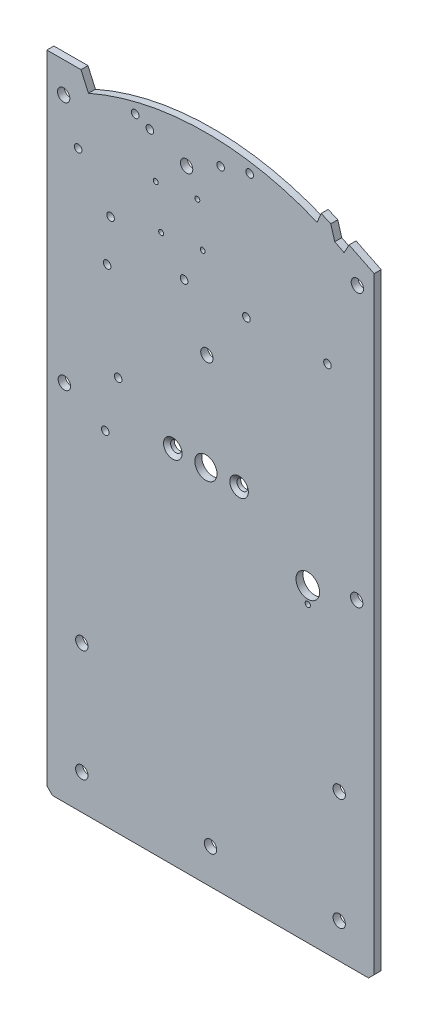
SolidWorks part; units mm, degrees
material "6061-T6 (SS)"
ref_plane "Front Plane" through (0, 0, 0) normal (0, 0, 1) x (1, 0, 0)
ref_plane "Top Plane" through (0, 0, 0) normal (0, 1, 0) x (1, 0, 0)
ref_plane "Right Plane" through (0, 0, 0) normal (1, 0, 0) x (0, 0, -1)
sketch "Sketch1" plane through (0, 0, 0) normal (0, 0, 1) x (1, 0, 0)
  line L0 (-37.0142, -65.193) -> (-37.0142, -242.993)
  line L1 (111.7057, -78.8372) -> (111.7057, -242.993)
  line L2 (111.7057, -242.993) -> (-37.0142, -242.993)
  line L3 (-28.4308, -65.1684) -> (-21.4969, -65.1485)
  line L4 (-21.4969, -65.1485) -> (-20.0556, -68.4088)
  line L41 (111.7057, -78.8372) -> (100.3159, -73.2191)
  line L42 (100.3159, -73.2191) -> (98.0489, -77.4075)
  line L43 (93.8204, -75.2164) -> (91.992, -69.0732)
  line L44 (91.992, -69.0732) -> (87.6255, -67.1718)
  line L45 (87.6255, -67.1718) -> (85.8005, -71.5708)
  line L46 (-18.13, -72.7646) -> (-20.0556, -68.4088)
  line L47 (-25.8634, -70.9762) -> (-28.4308, -65.1684) construction
  line L48 (-28.4308, -65.1684) -> (-37.0142, -65.193)
  line L75 (-20.0556, -68.4088) -> (-25.8634, -70.9762) construction
  arc A5 (98.0489, -77.4075) -> (93.8204, -75.2164) centre (35.2286, -193.468) ccw
  arc A9 (85.8005, -71.5708) -> (-18.13, -72.7646) centre (35.2286, -193.468) ccw
  dimension "D2" = 177.8
  dimension "D1" = 148.72
extrude "Boss-Extrude1" add sketch "Sketch1" against normal blind 3.175
sketch "Sketch2" plane through (0, 0, 0) normal (0, 0, 1) x (1, 0, 0)
  line L0 (111.7057, -231.472) -> (111.7057, -78.8372) construction
  line L1 (-21.4969, -65.1485) -> (-37.0142, -65.193) construction
  circle A0 centre (35.2684, -193.372) radius 5.0419
  dimension "D1" = 10.0838
  dimension "D2" = 76.4373
  dimension "D3" = 128.3861
extrude "Cut-Extrude1" cut sketch "Sketch2" against normal through all
hole_wizard "#4 Clearance Hole1" positions "Sketch4" profile "Sketch3" hole size "#4" standard "ANSI Inch" end condition through all
sketch "Sketch4" plane through (0, 0, 0) normal (0, 0, 1) x (1, 0, 0)
  point P0 (41.9398, -71.4888)
  point P3 (9.7895, -73.0113)
  point P6 (90.4886, -124.9671)
  point P9 (53.6587, -125.0729)
  point P12 (25.3388, -124.3417)
  point P15 (-9.6344, -135.8882)
  point P19 (55.1452, -67.7003)
  point P23 (3.102, -70.2707)
sketch "Sketch3" plane through (41.9398, -71.4888, 0) normal (1, 0, 0) x (0, -1, 0)
  line L0 (0, 0) -> (0, 3.175)
  line L1 (0, 3.175) -> (1.7272, 3.175)
  line L2 (1.7272, 3.175) -> (1.7272, 0)
  line L5 (1.7272, 0) -> (0, 0)
  line L11 (0, -6.35) -> (0, 107.95) construction
  dimension "Thru Hole Dia." = 3.4544
  dimension "Thru Hole Depth" = 3.175
hole_wizard "#10 Clearance Hole1" positions "Sketch6" profile "Sketch5" hole size "#10" standard "ANSI Inch" end condition through all
sketch "Sketch6" plane through (0, 0, 0) normal (0, 0, 1) x (1, 0, 0)
  point P0 (-29.3942, -79.072)
  point P3 (104.0857, -87.327)
  point P9 (35.696, -148.922)
  point P12 (26.4858, -79.072)
sketch "Sketch5" plane through (-29.3942, -79.072, 0) normal (1, 0, 0) x (0, -1, 0)
  line L0 (0, 0) -> (0, 3.175)
  line L1 (0, 3.175) -> (2.8067, 3.175)
  line L2 (2.8067, 3.175) -> (2.8067, 0)
  line L5 (2.8067, 0) -> (0, 0)
  line L11 (0, -6.35) -> (0, 107.95) construction
  dimension "Thru Hole Dia." = 5.6134
  dimension "Thru Hole Depth" = 3.175
hole_wizard "#4 Clearance Hole2" positions "Sketch8" profile "Sketch7" hole size "#4" standard "ANSI Inch" end condition through all
sketch "Sketch8" plane through (0, 0, 0) normal (0, 0, 1) x (1, 0, 0)
  point P0 (-8.0737, -116.3194)
  point P3 (-22.8122, -96.7821)
  point P12 (-10.4786, -201.738)
  point P15 (-4.604, -177.9805)
sketch "Sketch7" plane through (-8.0737, -116.3194, 0) normal (1, 0, 0) x (0, -1, 0)
  line L0 (0, 0) -> (0, 3.175)
  line L1 (0, 3.175) -> (1.7272, 3.175)
  line L2 (1.7272, 3.175) -> (1.7272, 0)
  line L5 (1.7272, 0) -> (0, 0)
  line L11 (0, -6.35) -> (0, 107.95) construction
  dimension "Thru Hole Dia." = 3.4544
  dimension "Thru Hole Depth" = 3.175
hole_wizard "27/64 (0.42188) Diameter Hole1" positions "Sketch10" profile "Sketch9" hole size "27/64" standard "ANSI Inch" end condition through all
sketch "Sketch10" plane through (0, 0, 0) normal (0, 0, 1) x (1, 0, 0)
  point P0 (81.5512, -216.6701)
sketch "Sketch9" plane through (81.5512, -216.6701, 0) normal (1, 0, 0) x (0, -1, 0)
  line L0 (0, 0) -> (0, 3.175)
  line L1 (0, 3.175) -> (5.3579, 3.175)
  line L2 (5.3579, 3.175) -> (5.3579, 0)
  line L5 (5.3579, 0) -> (0, 0)
  line L11 (0, -6.35) -> (0, 107.95) construction
  dimension "Thru Hole Dia." = 10.7158
  dimension "Thru Hole Depth" = 3.175
hole_wizard "3/32 (0.09375) Diameter Hole1" positions "Sketch12" profile "Sketch11" hole size "3/32" standard "ANSI Inch" end condition through all
sketch "Sketch12" plane through (0, 0, 0) normal (0, 0, 1) x (1, 0, 0)
  circle A0 centre (81.5512, -216.6701) radius 5.3579 construction
  point P0 (81.5512, -224.0361)
  dimension "D1" = 7.366
sketch "Sketch11" plane through (81.5512, -224.0361, 0) normal (1, 0, 0) x (0, -1, 0)
  line L0 (0, 0) -> (0, 3.175)
  line L1 (0, 3.175) -> (1.1906, 3.175)
  line L2 (1.1906, 3.175) -> (1.1906, 0)
  line L5 (1.1906, 0) -> (0, 0)
  line L11 (0, -6.35) -> (0, 107.95) construction
  dimension "Thru Hole Dia." = 2.3812
  dimension "Thru Hole Depth" = 3.175
hole_wizard "#10 Clearance Hole2" positions "Sketch14" profile "Sketch13" hole size "#10" standard "ANSI Inch" end condition through all
sketch "Sketch14" plane through (0, 0, 0) normal (0, 0, 1) x (1, 0, 0)
  circle A0 centre (-29.0767, -192.193) radius 2.8067 construction
  circle A1 centre (103.7682, -211.243) radius 2.8067 construction
  point P0 (-29.0767, -192.193)
  point P6 (103.7682, -211.243)
sketch "Sketch13" plane through (-29.0767, -192.193, 0) normal (1, 0, 0) x (0, -1, 0)
  line L0 (0, 0) -> (0, 3.175)
  line L1 (0, 3.175) -> (2.8067, 3.175)
  line L2 (2.8067, 3.175) -> (2.8067, 0)
  line L5 (2.8067, 0) -> (0, 0)
  line L11 (0, -6.35) -> (0, 107.95) construction
  dimension "Thru Hole Dia." = 5.6134
  dimension "Thru Hole Depth" = 3.175
sketch "Sketch15" plane through (0, 0, 0) normal (0, 0, 1) x (1, 0, 0)
  line L0 (109.1657, -357.293) -> (-34.4742, -357.293) construction
  line L1 (-37.0142, -242.993) -> (111.7057, -242.993)
  line L2 (-37.0142, -242.993) -> (-37.0142, -357.293)
  line L3 (-37.0142, -357.293) -> (111.7057, -357.293)
  line L4 (111.7057, -242.993) -> (111.7057, -357.293)
extrude "Boss-Extrude2" add sketch "Sketch15" against normal through all
chamfer "Chamfer1" distance 2.54 angle 45 2 edges at (-37.0142, -357.293, -1.5875) (111.7057, -357.293, -1.5875)
hole_wizard "#10 Clearance Hole3" positions "Sketch16" profile "Sketch17" hole size "#10" standard "ANSI Inch" end condition through all
sketch "Sketch16" plane through (0, 0, 0) normal (0, 0, 1) x (1, 0, 0)
  point P0 (95.8307, -341.418)
  point P3 (37.3457, -341.418)
  point P6 (-21.1392, -341.418)
  point P9 (95.8307, -290.618)
  point P12 (-21.1392, -290.618)
sketch "Sketch17" plane through (95.8307, -341.418, 0) normal (1, 0, 0) x (0, -1, 0)
  line L0 (0, 0) -> (0, 3.175)
  line L1 (0, 3.175) -> (2.8067, 3.175)
  line L2 (2.8067, 3.175) -> (2.8067, 0)
  line L5 (2.8067, 0) -> (0, 0)
  line L11 (0, -6.35) -> (0, 107.95) construction
  dimension "Thru Hole Dia." = 5.6134
  dimension "Thru Hole Depth" = 3.175
hole_wizard "CSK for #8 Flat Head Machine Screw (100)2" positions "Sketch18" profile "Sketch19" countersink size "#8" standard "ANSI Inch" end condition through all
sketch "Sketch18" plane through (0, 0, 0) normal (0, 0, 1) x (1, 0, 0)
  circle A0 centre (20.203, -193.372) radius 4.2164 construction
  circle A1 centre (50.3338, -193.372) radius 4.2164 construction
  point P0 (20.203, -193.372)
  point P2 (50.3338, -193.372)
sketch "Sketch19" plane through (20.203, -193.372, 0) normal (1, 0, 0) x (0, -1, 0)
  line L0 (0, 0) -> (0, 3.175)
  line L1 (0, 3.175) -> (2.4574, 3.175)
  line L2 (2.4574, 3.175) -> (2.4574, 1.4759)
  line L3 (2.4574, 1.4759) -> (4.2164, 0)
  line L5 (4.2164, 0) -> (0, 0)
  line L6 (-2.4574, 1.4759) -> (-4.2164, 0) construction
  line L11 (0, -6.35) -> (0, 107.95) construction
  dimension "Thru Hole Dia." = 4.9149
  dimension "Thru Hole Depth" = 3.175
  dimension "Near C'Sink Dia." = 8.4328
  dimension "Near C'Sink Angle" = 100
hole_wizard "#4-40 Tapped Hole1" positions "Sketch20" profile "Sketch21" tap size "#4-40" standard "ANSI Inch" end condition through all
sketch "Sketch20" plane through (0, 0, 0) normal (0, 0, 1) x (1, 0, 0)
  point P7 (31.3544, -89.7014)
  point P10 (12.4643, -92.1648)
  point P13 (14.9278, -111.0549)
  point P16 (33.8178, -108.5914)
sketch "Sketch21" plane through (31.3544, -89.7014, 0) normal (1, 0, 0) x (0, -1, 0)
  line L0 (0, 0) -> (0, 3.175)
  line L1 (0, 3.175) -> (1.1303, 3.175)
  line L2 (1.1303, 3.175) -> (1.1303, 0)
  line L5 (1.1303, 0) -> (0, 0)
  line L11 (0, -6.35) -> (0, 107.95) construction
  dimension "Thru Tap Drill Dia." = 2.2606
  dimension "Thru Tap Drill Depth" = 3.175
cosmetic thread "Hole Thread1" parameters "D2"=2.8448
cosmetic thread "Hole Thread2" parameters "D2"=2.8448
cosmetic thread "Hole Thread3" parameters "D2"=2.8448
cosmetic thread "Hole Thread4" parameters "D2"=2.8448
